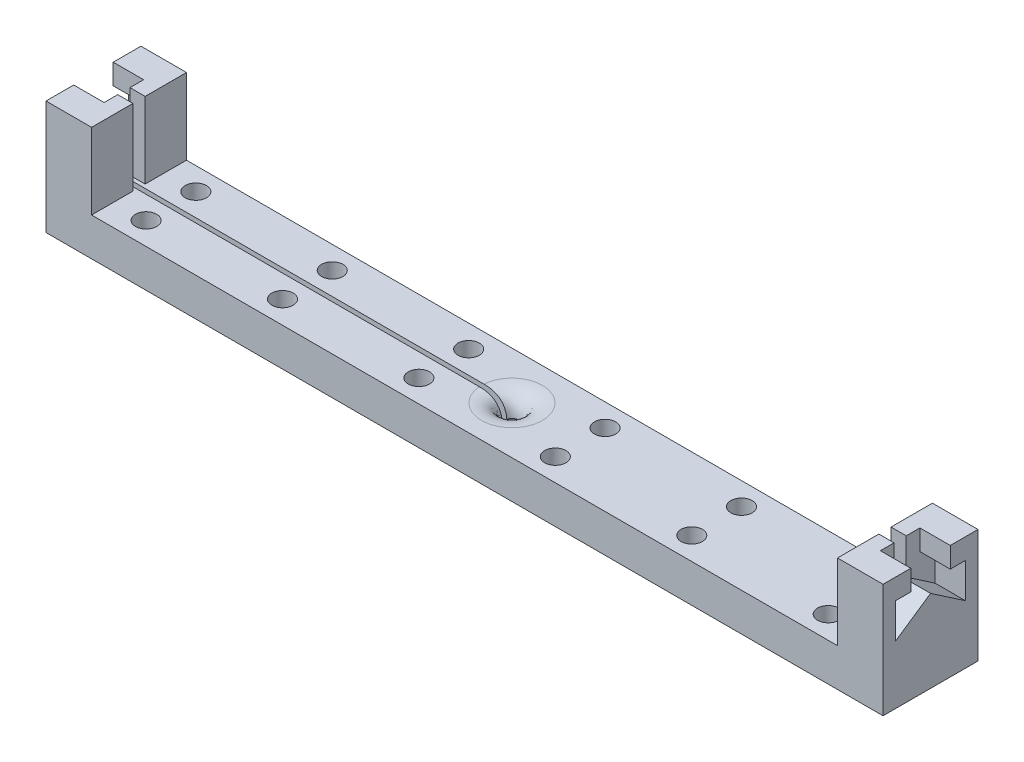
SolidWorks part; units mm, degrees
ref_plane "Front Plane" through (0, 0, 0) normal (0, 0, 1) x (1, 0, 0)
ref_plane "Top Plane" through (0, 0, 0) normal (0, 1, 0) x (1, 0, 0)
ref_plane "Right Plane" through (0, 0, 0) normal (1, 0, 0) x (0, 0, -1)
sketch "Sketch1" plane through (0, 0, 0) normal (0, 1, 0) x (1, 0, 0)
  line L0 (0.254, 7.9375) -> (139.954, 7.9375) construction
  line L2 (0, 0) -> (0, 15.875)
  line L4 (139.954, 0) -> (139.954, 15.875)
  line L5 (0, 0) -> (5.08, 0)
  line L7 (0, 15.875) -> (5.08, 15.875)
  line L8 (5.08, 0) -> (5.08, 15.875)
  line L9 (139.954, 0) -> (134.874, 0)
  line L11 (139.954, 15.875) -> (134.874, 15.875)
  line L12 (134.874, 0) -> (134.874, 15.875)
  line L21 (0, 8.3185) -> (69.977, 8.3185)
  line L23 (0, 7.5565) -> (69.977, 7.5565)
  line L24 (69.977, 8.3185) -> (69.977, 7.5565)
  line L25 (69.977, 15.875) -> (69.977, 0) construction
  line L26 (11.1904, 2.0003) -> (14.7176, 2.0003) construction
  line L27 (5.08, 15.875) -> (134.874, 15.875)
  line L29 (5.08, 0) -> (134.874, 0)
  line L31 (11.1904, 13.8747) -> (14.7176, 13.8747) construction
  line L32 (12.954, 0) -> (12.954, 7.5565) construction
  line L33 (68.7655, 8.3185) -> (68.6928, 8.0873)
  circle A0 centre (12.954, 3.7783) radius 1.778
  circle A27 centre (69.977, 7.9375) radius 1.27
  circle A47 centre (35.7632, 3.7783) radius 1.778
  circle A48 centre (58.5724, 3.7783) radius 1.778
  circle A49 centre (81.3816, 3.7783) radius 1.778
  circle A50 centre (104.1908, 3.7783) radius 1.778
  circle A51 centre (127, 3.7783) radius 1.778
  circle A52 centre (127, 12.0967) radius 1.778
  circle A53 centre (104.1908, 12.0967) radius 1.778
  circle A54 centre (81.3816, 12.0967) radius 1.778
  circle A55 centre (58.5724, 12.0967) radius 1.778
  circle A56 centre (35.7632, 12.0967) radius 1.778
  circle A57 centre (12.954, 12.0967) radius 1.778
  point P11 (12.954, 2.0003)
  point P14 (12.954, 3.7783)
  point P72 (69.977, 15.875)
  dimension "D7" = 7.874
  dimension "D8" = 2.0003
  dimension "D4" = 3.556
  dimension "D10" = 2.54
  dimension "D1" = 15.875
  dimension "D2" = 139.954
  dimension "D3" = 5.08
  dimension "D5" = 0.762
  dimension "D6" = 69.977
  dimension "D9" = 129.794
  dimension "D11" = 6
extrude "Boss-Extrude1" add sketch "Sketch1" along normal blind 19.05 contours L2 L21 L8 | L23 L8 | L12 L9 L4 | L12 | A27 L23 L8 L29 L12 L27 L21 A56 A54 A52 A51 A50 A49 A48 A47 A0 A53 A55 A57 region at (2.54, 0, -3.7783) region at (6.3876, 0, -3.7782) region at (2.54, 0, -12.0967) region at (137.414, 0, -7.9375)
sketch "Sketch2" plane through (139.954, 0, 0) normal (1, 0, 0) x (0, 0, -1)
  line L0 (0, 0) -> (15.875, 0) construction
  line L1 (7.9375, 0) -> (7.9375, 19.05) construction
  line L3 (7.9375, 13.7622) -> (17.6378, 13.7622) construction
  line L10 (11.2395, 19.05) -> (4.6355, 19.05)
  line L11 (0, 19.05) -> (15.875, 19.05) construction
  line L12 (4.6355, 19.05) -> (4.6355, 15.621)
  line L13 (4.6355, 15.621) -> (2.0955, 15.621)
  line L14 (2.0955, 15.621) -> (2.0955, 9.779)
  line L15 (2.0955, 9.779) -> (7.9375, 13.7622)
  line L16 (7.9375, 13.7622) -> (7.9375, 19.05)
  line L17 (13.7795, 9.779) -> (7.9375, 13.7622)
  line L18 (13.7795, 15.621) -> (13.7795, 9.779)
  line L19 (11.2395, 15.621) -> (13.7795, 15.621)
  line L20 (11.2395, 19.05) -> (11.2395, 15.621)
  line L21 (17.6378, 13.7622) -> (17.6378, 19.05) construction
  line L22 (17.6378, 19.05) -> (7.9375, 19.05) construction
  line L23 (2.0955, 9.779) -> (17.6378, 9.779) construction
  line L24 (17.6378, 9.779) -> (17.6378, 13.7622) construction
  point P8 (7.9375, 0)
  line M9 (15.875, 19.05) -> (0, 19.05)
  dimension "D1" = 15.875
  dimension "D2" = 3.302
  dimension "D3" = 3.429
  dimension "D4" = 5.842
  dimension "D5" = 2.54
  dimension "D6" = 5.2878
  dimension "D7" = 55.713
  dimension "D8" = 3.9832
  dimension "D9" = 1.8588
extrude "Cut-Extrude1" cut sketch "Sketch2" against normal through all contours L15 L16 L10 L12 L13 L14 | L20 L16 L17 L18 L19 M9 | L15 L14 L13 L12 L10 L20 L19 L18 L17 region at (139.954, 14.8002, -10.7683) region at (139.954, 14.8002, -5.1067)
sketch "Sketch4" plane through (0, 0, -15.875) normal (0, 0, -1) x (-1, 0, 0)
  line L0 (-69.977, 19.05) -> (-69.977, 0) construction
  line L1 (0, 19.05) -> (-139.954, 19.05) construction
  line L2 (0, 0) -> (-139.954, 0) construction
  line L3 (-134.874, 19.05) -> (-134.874, 6.35)
  line L4 (-134.874, 6.35) -> (-5.08, 6.35)
  line L5 (-69.977, 6.35) -> (-69.977, 19.05)
  line L6 (-5.08, 19.05) -> (-134.874, 19.05)
  line L7 (-139.954, 19.05) -> (-139.954, 0) construction
  line L8 (-5.08, 19.05) -> (-5.08, 6.35)
  line M8 (0, 19.05) -> (-139.954, 19.05)
  dimension "D1" = 5.08
  dimension "D2" = 12.7
extrude "Cut-Extrude6" cut sketch "Sketch4" against normal through all contours L4 L5 L3 M8 | L8 L5 L4 M8 region at (102.4255, 12.7, -15.875) region at (37.5285, 12.7, -15.875)
sketch "Sketch5" plane through (0, 6.35, 0) normal (0, 1, 0) x (1, 0, 0)
  line L0 (134.874, 15.875) -> (132.334, 15.875)
  line L1 (134.874, 15.875) -> (5.08, 15.875) construction
  line L2 (132.334, 15.875) -> (132.334, 0)
  line L3 (134.874, 0) -> (5.08, 0) construction
  line L4 (132.334, 0) -> (134.874, 0)
  line L5 (134.874, 0) -> (134.874, 15.875)
  line L6 (139.7, 7.9375) -> (0, 7.9375) construction
  line L7 (5.08, 8.3185) -> (7.62, 8.3185)
  line L8 (69.977, 15.875) -> (69.977, 0) construction
  line L9 (2.588, 8.3185) -> (2.588, 7.5565) construction
  line L10 (2.588, 8.001) -> (2.588, 7.874) construction
  line L11 (0.604, 8.3185) -> (2.588, 8.3185) construction
  line L12 (3.096, 8.3185) -> (3.096, 7.5565) construction
  line L13 (68.7655, 8.3185) -> (5.08, 8.3185) construction
  line L14 (2.588, 8.3185) -> (3.096, 8.3185) construction
  line L15 (3.096, 8.3185) -> (5.08, 8.3185) construction
  line L16 (5.08, 8.3185) -> (5.08, 15.875) construction
  line L17 (0.604, 7.5565) -> (2.588, 7.5565) construction
  line L18 (7.62, 8.3185) -> (7.62, 8.9535)
  line L19 (2.588, 7.5565) -> (3.096, 7.5565) construction
  line L20 (3.096, 7.5565) -> (5.08, 7.5565) construction
  line L21 (5.08, 0) -> (5.08, 7.5565) construction
  line L22 (5.08, 8.3185) -> (3.096, 8.001)
  line L24 (3.096, 8.001) -> (3.096, 7.874) construction
  line L25 (3.096, 8.001) -> (2.588, 8.001)
  line L26 (2.588, 8.001) -> (0.604, 8.3185)
  line L27 (0.604, 8.3185) -> (5.08, 8.3185)
  line L28 (0.604, 7.5565) -> (2.588, 7.874)
  line L29 (2.588, 7.874) -> (3.096, 7.874)
  line L30 (3.096, 7.874) -> (5.08, 7.5565)
  line L31 (5.08, 7.5565) -> (0.604, 7.5565)
  line L32 (7.62, 0) -> (5.08, 0)
  line L33 (7.62, 15.875) -> (7.62, 0)
  line L34 (5.08, 15.875) -> (7.62, 15.875)
  line L35 (5.08, 0) -> (5.08, 15.875)
  line L36 (7.62, 8.9535) -> (5.08, 8.9535)
  line L37 (5.08, 8.9535) -> (5.08, 8.3185)
  line L38 (7.62, 6.9215) -> (5.08, 6.9215)
  line L39 (7.62, 7.5565) -> (7.62, 6.9215)
  line L40 (5.08, 7.5565) -> (7.62, 7.5565)
  line L41 (5.08, 6.9215) -> (5.08, 7.5565)
  line L42 (132.334, 6.9215) -> (132.334, 8.9535)
  line L43 (132.334, 8.9535) -> (134.874, 8.9535)
  line L44 (134.874, 8.9535) -> (134.874, 6.9215)
  line L45 (134.874, 7.9375) -> (132.334, 7.9375)
  line L46 (132.334, 6.9215) -> (134.874, 6.9215)
  line L47 (68.7655, 8.3185) -> (68.7655, 7.5565) construction
  line L48 (68.7655, 8.3185) -> (68.6656, 8.001)
  line L49 (68.6656, 8.001) -> (68.3884, 8.001)
  line L50 (68.3884, 8.001) -> (66.4044, 8.3185)
  line L51 (66.4044, 8.3185) -> (68.7655, 8.3185)
  line L52 (68.3884, 7.874) -> (66.4044, 7.5565)
  line L53 (68.6656, 7.874) -> (68.3884, 7.874)
  line L54 (68.7655, 7.5565) -> (68.6656, 7.874)
  line L55 (66.4044, 7.5565) -> (68.7655, 7.5565)
  arc A0 (68.7655, 7.5565) -> (68.7655, 8.3185) centre (69.977, 7.9375) ccw construction
  point P23 (2.588, 7.9375)
  point P24 (2.588, 7.9375)
  line M37 (5.08, 0) -> (134.874, 0)
  line M38 (134.874, 0) -> (134.874, 15.875)
  line M39 (134.874, 15.875) -> (5.08, 15.875)
  line M40 (5.08, 15.875) -> (5.08, 8.3185)
  dimension "D1" = 0.127
  dimension "D2" = 0.508
  dimension "D3" = 2.54
  dimension "D4" = 0.635
  dimension "D5" = 1.016
  dimension "D6" = 2.032
  dimension "D7" = 0.762
  dimension "D8" = 2.032
  dimension "D9" = 9.092
  dimension "D10" = 0.127
extrude "Boss-Extrude3" add sketch "Sketch5" against normal blind 6.35 and the other way blind 7.112 contours L27 L26 L25 L22 | L31 L30 L29 L28 region at (2.842, 6.35, -8.2019) region at (2.842, 6.35, -7.6731)
extrude "Boss-Extrude4" add sketch "Sketch5<7>" along normal blind 12.7 contours L36 L33 M39 M40 | L33 L38 L35 M37 | L2 L43 L5 M39 | L46 L2 M37 M38 region at (133.604, 6.35, -12.4143) region at (6.35, 6.35, -12.4143) region at (133.604, 6.35, -3.4607) region at (6.35, 6.35, -3.4607)
sketch "Sketch5<7>" plane through (0, 6.35, 0) normal (0, 1, 0) x (1, 0, 0) same geometry as "Sketch5"
fillet "Fillet1" radius 3.81 2 edges at (71.247, 0, -7.9375) (71.247, 6.35, -7.9375) conic rho 0.5
